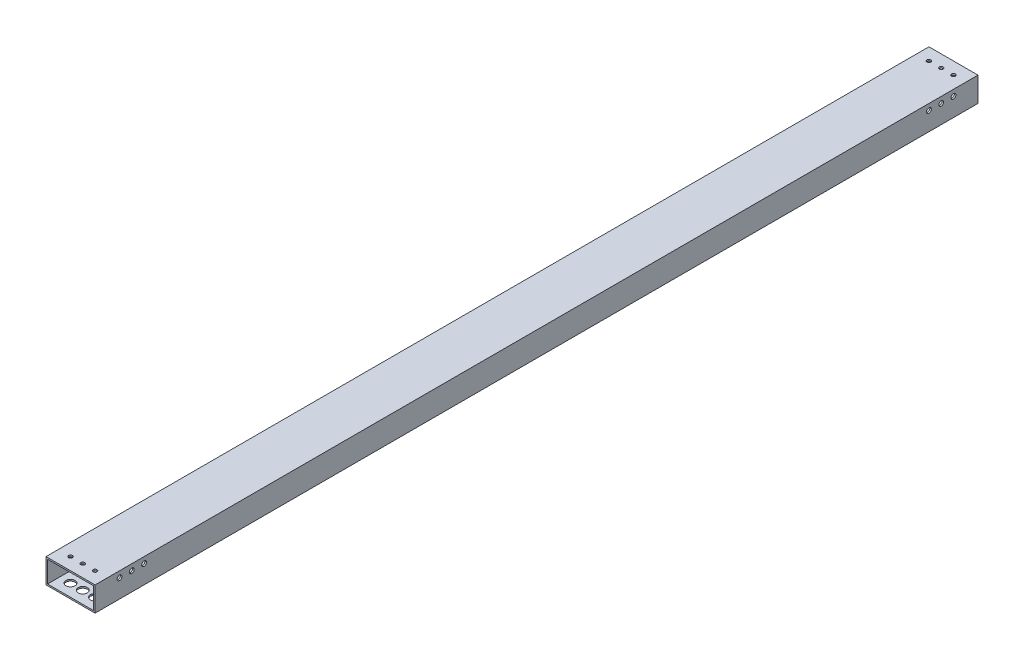
SolidWorks part; units mm, degrees
other "Markup1"
sketch "Sketch5" plane through (-25.4, -12.7, -457.2) normal (-0.35, -0.9329, -0.0852) x (-0.8023, 0.2515, 0.5413)
sketch "Sketch6" plane through (-25.4, -12.7, -457.2) normal (-0.35, -0.9329, -0.0852) x (-0.8023, 0.2515, 0.5413)
material "6061-T6 (SS)"
ref_plane "Front Plane" through (0, 0, 0) normal (0, 0, 1) x (1, 0, 0)
ref_plane "Top Plane" through (0, 0, 0) normal (0, 1, 0) x (1, 0, 0)
ref_plane "Right Plane" through (0, 0, 0) normal (1, 0, 0) x (0, 0, -1)
sketch "Sketch1" plane through (0, 0, 0) normal (0, 0, 1) x (1, 0, 0)
  line L0 (-23.8125, 11.1125) -> (23.8125, 11.1125)
  line L1 (-25.4, -12.7) -> (25.4, -12.7)
  line L2 (-25.4, -12.7) -> (-25.4, 12.7)
  line L3 (-25.4, 12.7) -> (25.4, 12.7)
  line L4 (25.4, -12.7) -> (25.4, 12.7)
  line L5 (-25.4, -12.7) -> (25.4, 12.7) construction
  line L6 (-25.4, 12.7) -> (25.4, -12.7) construction
  line L7 (23.8125, -11.1125) -> (23.8125, 11.1125)
  line L8 (-23.8125, -11.1125) -> (23.8125, -11.1125)
  line L9 (-23.8125, -11.1125) -> (-23.8125, 11.1125)
  point P0 (0, 0)
  dimension "D1" = 50.8
  dimension "D2" = 25.4
  dimension "D3" = 1.5875
extrude "Boss-Extrude1" add sketch "Sketch1" along normal mid plane 914.4
sketch "Sketch3" plane through (0, 12.7, 0) normal (0, 1, 0) x (1, 0, 0)
  line L2 (25.4, -457.2) -> (-25.4, -457.2) construction
  line L3 (25.4, 0) -> (-25.4, 0) construction
  line L4 (25.4, -457.2) -> (25.4, 457.2) construction
  line L5 (-25.4, -457.2) -> (-25.4, 457.2) construction
  circle A0 centre (0, -444.5) radius 2.0193
  circle A1 centre (12.7, -444.5) radius 2.0193
  circle A2 centre (-12.7, -444.5) radius 2.0193
  circle A3 centre (12.7, 444.5) radius 2.0193
  circle A4 centre (0, 444.5) radius 2.0193
  circle A5 centre (-12.7, 444.5) radius 2.0193
  dimension "D1" = 4.0386
  dimension "D2" = 12.7
  dimension "D3" = 12.7
  dimension "D4" = 12.7
extrude "Cut-Extrude2" cut sketch "Sketch3" against normal up to surface (1.5875 mm away) up to face at (0, 11.1125, 0)
sketch "Sketch4" plane through (0, -12.7, 0) normal (0, -1, 0) x (1, 0, 0)
  circle A0 centre (-12.7, 444.5) radius 2.0193 construction
  circle A1 centre (0, 444.5) radius 2.0193 construction
  circle A2 centre (12.7, 444.5) radius 2.0193 construction
  circle A3 centre (-12.7, 444.5) radius 2.0193
  circle A4 centre (0, 444.5) radius 2.0193
  circle A5 centre (12.7, 444.5) radius 2.0193
  circle A6 centre (-12.7, -444.5) radius 2.0193 construction
  circle A7 centre (0, -444.5) radius 2.0193 construction
  circle A8 centre (12.7, -444.5) radius 2.0193 construction
  circle A9 centre (-12.7, -444.5) radius 2.0193
  circle A10 centre (0, -444.5) radius 2.0193
  circle A11 centre (12.7, -444.5) radius 2.0193
  circle A12 centre (-12.7, 444.5) radius 4.7625
  circle A13 centre (0, 444.5) radius 4.7625
  circle A14 centre (12.7, 444.5) radius 4.7625
  circle A15 centre (-12.7, -444.5) radius 4.7625
  circle A16 centre (0, -444.5) radius 4.7625
  circle A17 centre (12.7, -444.5) radius 4.7625
  dimension "D1" = 9.525
  dimension "D2" = 9.525
extrude "Cut-Extrude4" cut sketch "Sketch4" against normal up to surface (1.5875 mm away) contours A12 A3 | A13 A4 | A4 | A3 | A5 | A14 A5 | A11 | A17 A11 | A16 A10 | A10 | A15 A9 | A9 region at (-12.7, -12.7, 444.5) region at (0, -12.7, 444.5) region at (12.7, -12.7, 444.5) region at (-12.7, -12.7, -444.5) region at (0, -12.7, -444.5) region at (12.7, -12.7, -444.5) region at (-17.3278, -12.7, 444.5) region at (-4.6278, -12.7, 444.5) region at (8.0722, -12.7, 444.5) region at (-17.3278, -12.7, -444.5) region at (-4.6278, -12.7, -444.5) region at (8.0722, -12.7, -444.5) up to face at (0, -11.1125, 0)
sketch "Sketch7" plane through (25.4, 0, 0) normal (1, 0, 0) x (0, 0, -1)
  line L0 (-457.2, -12.7) -> (-457.2, 12.7) construction
  line L1 (-457.2, 12.7) -> (457.2, 12.7) construction
  line L2 (0, 12.7) -> (0, -12.7) construction
  line L3 (-457.2, -12.7) -> (457.2, -12.7) construction
  circle A0 centre (-444.5, 6.35) radius 2.4892
  circle A1 centre (-431.8, 6.35) radius 2.4892
  circle A2 centre (-419.1, 6.35) radius 2.4892
  circle A3 centre (-406.4, 6.35) radius 2.4892
  circle A4 centre (406.4, 6.35) radius 2.4892
  circle A5 centre (419.1, 6.35) radius 2.4892
  circle A6 centre (431.8, 6.35) radius 2.4892
  circle A7 centre (444.5, 6.35) radius 2.4892
  dimension "D3" = 4.9784
  dimension "D1" = 12.7
  dimension "D2" = 6.35
  dimension "D4" = 12.7
  dimension "D5" = 12.7
  dimension "D6" = 12.7
extrude "Cut-Extrude5" cut sketch "Sketch7" against normal through all contours A1 | A2 | A3 | A5 | A4 | A6 region at (25.4, 6.35, 431.8) region at (25.4, 6.35, 419.1) region at (25.4, 6.35, 406.4) region at (25.4, 6.35, -406.4) region at (25.4, 6.35, -419.1) region at (25.4, 6.35, -431.8)
